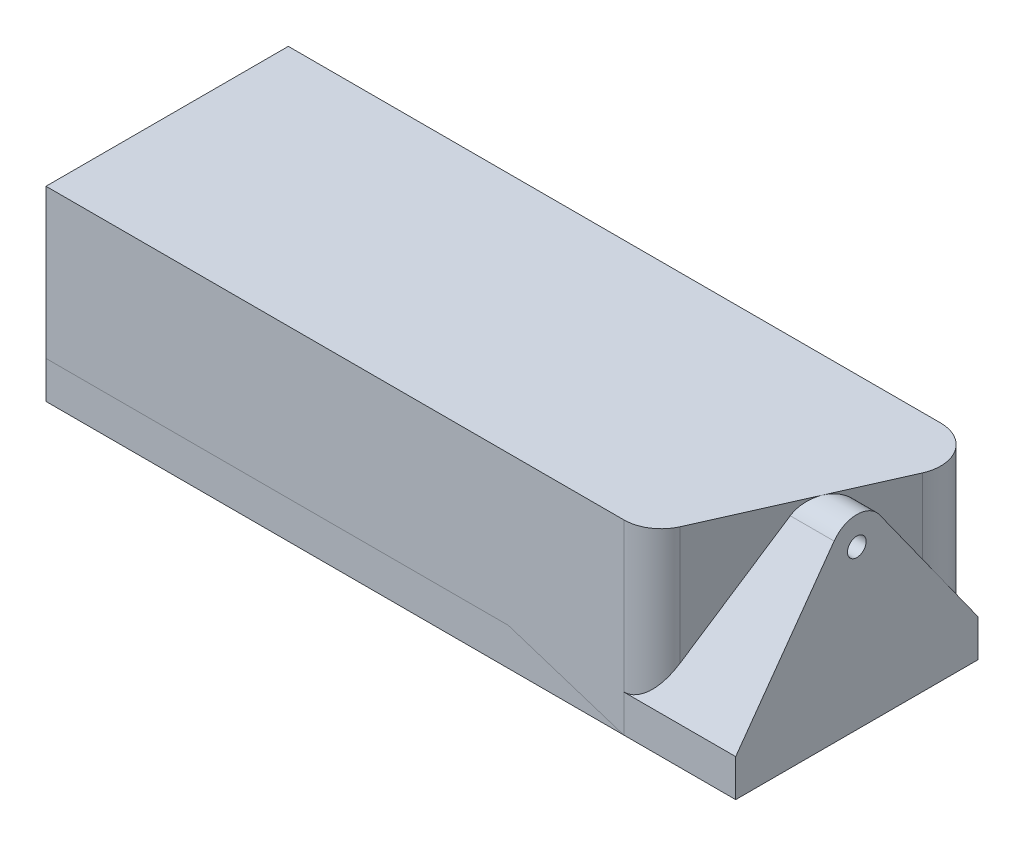
SolidWorks part; units mm, degrees
ref_plane "Front Plane" through (0, 0, 0) normal (0, 0, 1) x (1, 0, 0)
ref_plane "Top Plane" through (0, 0, 0) normal (0, 1, 0) x (1, 0, 0)
ref_plane "Right Plane" through (0, 0, 0) normal (1, 0, 0) x (0, 0, -1)
sketch "Sketch1" plane through (0, 0, 0) normal (0, 1, 0) x (1, 0, 0)
  line L0 (0, -10.3187) -> (0, 10.3187)
  line L1 (0, 10.3187) -> (55.5625, 10.3188)
  line L2 (58.4639, 5.8543) -> (52.1139, -8.4332)
  line L3 (49.2125, -10.3187) -> (0, -10.3187)
  arc A0 (55.5625, 10.3188) -> (58.4639, 5.8543) centre (55.5625, 7.1437) cw
  arc A1 (52.1139, -8.4332) -> (49.2125, -10.3187) centre (49.2125, -7.1437) cw
  point P4 (0, 0)
  point P11 (46.0375, 10.3187)
  dimension "D4" = 3.175
  dimension "D1" = 20.6375
  dimension "D2" = 46.0375
  dimension "D3" = 9.525
  dimension "D5" = 6.35
sketch "Sketch2" plane through (0, 0, 0) normal (0, 0, 1) x (1, 0, 0)
  line L0 (0, 0) -> (0, 3.175)
  line L1 (0, 3.175) -> (1.5875, 3.175)
  line L2 (1.5875, 3.175) -> (1.5875, 15.875)
  line L3 (1.5875, 15.875) -> (3.9688, 15.875)
  line L4 (3.9688, 15.875) -> (3.9688, 3.175)
  line L5 (3.9688, 3.175) -> (7.1438, 3.175)
  line L6 (7.1438, 3.175) -> (7.1438, 15.875)
  line L7 (7.1438, 15.875) -> (9.525, 15.875)
  line L8 (9.525, 15.875) -> (9.525, 3.175)
  line L9 (9.525, 3.175) -> (58.7375, 3.175)
  line L10 (58.7375, 3.175) -> (58.7375, 0)
  line L11 (58.7375, 0) -> (0, 0)
  dimension "D1" = 3.175
  dimension "D2" = 1.5875
  dimension "D3" = 12.7
  dimension "D4" = 2.3813
  dimension "D5" = 3.175
  dimension "D6" = 58.7375
sketch "Sketch3" plane through (0, 0, 0) normal (1, 0, 0) x (0, 0, -1)
  line L0 (10.3187, 0) -> (-10.3187, 0)
  line L2 (-10.3187, 0) -> (-10.3187, 3.175)
  line L3 (-10.3187, 3.175) -> (-1.936, 14.8802)
  line L4 (1.936, 14.8802) -> (10.3187, 3.175)
  line L5 (10.3187, 3.175) -> (10.3187, 0)
  arc A0 (-1.936, 14.8802) -> (1.936, 14.8802) centre (0, 13.4937) cw
  circle A1 centre (0, 13.4937) radius 0.7937
  point P4 (0, 0)
  dimension "D4" = 2.3813
  dimension "D1" = 20.6375
  dimension "D5" = 1.5875
  dimension "D2" = 3.175
  dimension "D3" = 10.3187
extrude "Boss-Extrude1" add sketch "Sketch1" along normal blind 15.875
extrude "Boss-Extrude2" add sketch "Sketch2" along normal blind 10.3187 and the other way blind 10.3187 separate body
extrude "Boss-Extrude3" add sketch "Sketch3" along normal blind 58.7375 separate body
equation "\"D6@Sketch2\"= \"D2@Sketch1\" + \"D3@Sketch1\" + \"D4@Sketch1\""
equation "\"D1@Sketch3\" = \"D1@Sketch1\""
equation "\"D2@Sketch3\"= \"D1@Sketch2\""
equation "\"D3@Sketch2\"= \"D3@Sketch3\" + \"D4@Sketch3\""
equation "\"D1@Boss-Extrude1\"= \"D1@Sketch2\" + \"D3@Sketch3\" + \"D4@Sketch3\""
equation "\"D1@Boss-Extrude2\" = \"D1@Sketch1\" / 2"
equation "\"D2@Boss-Extrude2\"= \"D1@Boss-Extrude2\""
equation "\"D1@Boss-Extrude3\"= \"D2@Sketch1\" + \"D3@Sketch1\" + \"D4@Sketch1\""
